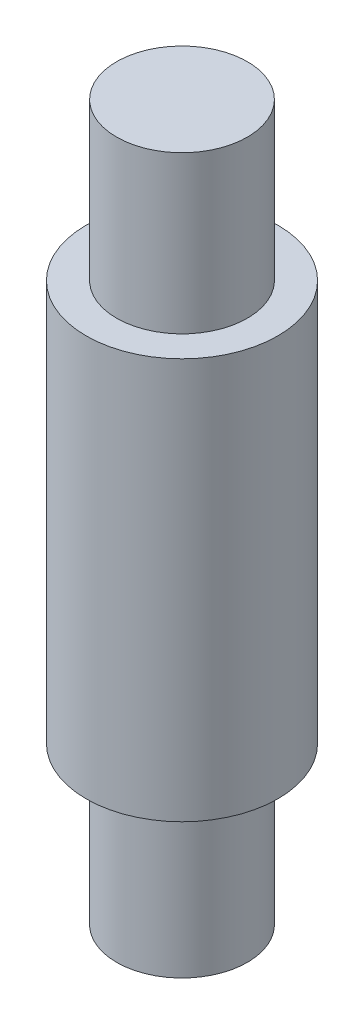
SolidWorks part; units mm, degrees
material "Plain Carbon Steel"
ref_plane "Front Plane" through (0, 0, 0) normal (0, 0, 1) x (1, 0, 0)
ref_plane "Top Plane" through (0, 0, 0) normal (0, 1, 0) x (1, 0, 0)
ref_plane "Right Plane" through (0, 0, 0) normal (1, 0, 0) x (0, 0, -1)
sketch "Sketch1" plane through (0, 0, 0) normal (0, 1, 0) x (1, 0, 0)
  circle A0 centre (0, 0) radius 7.5
  circle A1 centre (0, 0) radius 11
  dimension "D1" = 22
  dimension "D2" = 15
extrude "Boss-Extrude1" add sketch "Sketch1" along normal mid plane 46 contours A1
extrude "Boss-Extrude2" add sketch "Sketch1<3>" along normal mid plane 82 contours A0
sketch "Sketch1<3>" plane through (0, 0, 0) normal (0, 1, 0) x (1, 0, 0) same geometry as "Sketch1"
cosmetic thread "Cosmetic Thread1"
cosmetic thread "Cosmetic Thread2"
